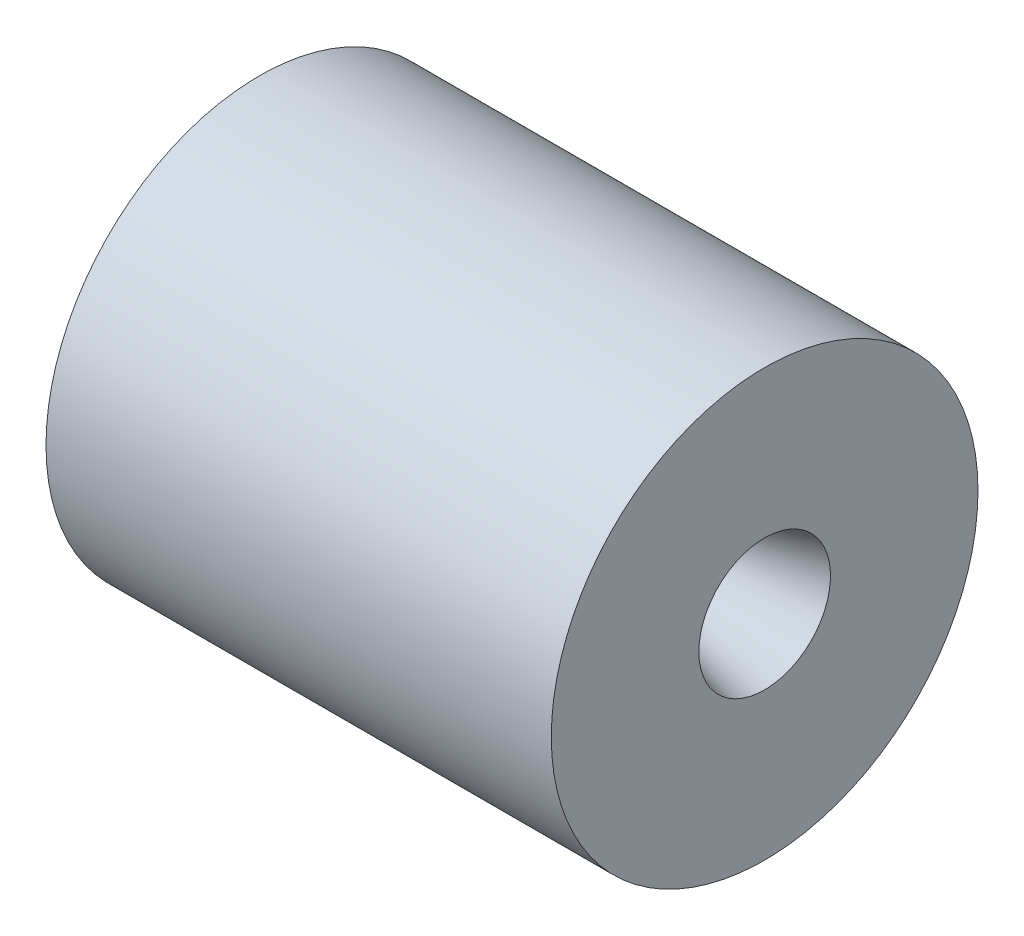
SolidWorks part; units mm, degrees
material "AISI 304"
ref_plane "Front Plane" through (0, 0, 0) normal (0, 0, 1) x (1, 0, 0)
ref_plane "Top Plane" through (0, 0, 0) normal (0, 1, 0) x (1, 0, 0)
ref_plane "Right Plane" through (0, 0, 0) normal (1, 0, 0) x (0, 0, -1)
sketch "Sketch1" plane through (0, 0, 0) normal (0, 0, 1) x (1, 0, 0)
  line L0 (0, 0) -> (366.3783, 0) construction
  line L1 (0, 0) -> (0, 38.1) construction
  line L2 (0, 38.1) -> (110.897, 38.1)
  line L3 (158.9188, 24.511) -> (158.9188, 13.97) construction
  line L4 (117.247, 36.3985) -> (153.6483, 15.3822)
  line L5 (150.9294, 13.97) -> (106.9103, 13.97) construction
  line L6 (161.647, 14.3292) -> (210.5452, 27.4314)
  line L7 (210.5452, 27.4314) -> (210.5452, 0) construction
  line L13 (160.3322, 19.2361) -> (209.2304, 32.3383) construction
  line L17 (0, 43.18) -> (110.897, 43.18) construction
  line L18 (119.787, 40.7979) -> (156.1883, 19.7816) construction
  line L19 (0, 38.1) -> (0, 45.72)
  line L20 (0, 88.9) -> (210.5452, 88.9)
  line L21 (210.5452, 88.9) -> (210.5452, 27.4314)
  line L22 (0, 45.72) -> (5.08, 45.72)
  line L23 (5.08, 45.72) -> (5.08, 55.88)
  line L24 (5.08, 55.88) -> (0, 55.88)
  line L25 (0, 55.88) -> (0, 88.9)
  arc A0 (153.6483, 15.3822) -> (161.647, 14.3292) centre (158.9188, 24.511) ccw
  arc A1 (110.897, 38.1) -> (117.247, 36.3985) centre (110.897, 25.4) cw
  arc A3 (156.1883, 19.7816) -> (160.3322, 19.2361) centre (158.9188, 24.511) ccw
  arc A4 (110.897, 43.18) -> (119.787, 40.7979) centre (110.897, 25.4) cw construction
  point P16 (114.3, 38.1)
  point P29 (5.08, 50.8)
  dimension "D4" = 21.082
  dimension "D9" = 12.7
  dimension "D1" = 38.1
  dimension "D2" = 114.3
  dimension "D3" = 13.97
  dimension "D5" = 30
  dimension "D6" = 15
  dimension "D7" = 27.4314
  dimension "D11" = 50.8
  dimension "D12" = 10.16
  dimension "D13" = 12.7
  dimension "D14" = 5.08
  dimension "D10" = 5.08
revolve "Revolve1" add sketch "Sketch1" angle 360 about L0 region at (113.2306, 59.3604, 0)
sketch "Sketch3" plane through (0, 0, 0) normal (-1, 0, 0) x (0, 0, 1)
  circle A0 centre (0, 0) radius 69.85 construction
  circle A1 centre (-69.85, 0) radius 6.35
  circle A2 centre (-21.5848, 66.4313) radius 6.35
  circle A3 centre (56.5098, 41.0568) radius 6.35
  circle A4 centre (56.5098, -41.0568) radius 6.35
  circle A5 centre (-21.5848, -66.4313) radius 6.35
  point P15 (0, 0)
  dimension "D1" = 139.7
  dimension "D2" = 12.7
  dimension "D3" = 5
extrude "Cut-Extrude2" cut sketch "Sketch3" against normal blind 25.4
equation "\"l_star\"= .8m'characteristic length"
equation "\"R_t\"= .55in'throat radius"
equation "\"V_c\"= \"l_star\" * \"R_t\"'chamber volume"
equation "\"D_c\"= 3in'chamber diameter"
equation "\"L_c\"= \"V_c\" / ( ( pi * \"D_c\" ) / 4 )'chamber length"
equation "\"eps_x\"= 3.8557'expansion ratio"
equation "\"D_e\"= \"R_t\" * 2 * sqr ( \"eps_x\" )'exit diameter"
equation "\"arc_t\"= 1.5in * \"R_t\"'arc between convergent and divergent"
equation "\"D3@Sketch1\"=\"R_t\""
equation "\"D7@Sketch1\"=\"D_e\"/2"
equation "\"D1@Sketch1\"=\"D_c\"/2"
equation "\"D13@Sketch1\"=\"D11@Sketch1\"/4"
equation "\"D14@Sketch1\"=\"D12@Sketch1\"/2"
